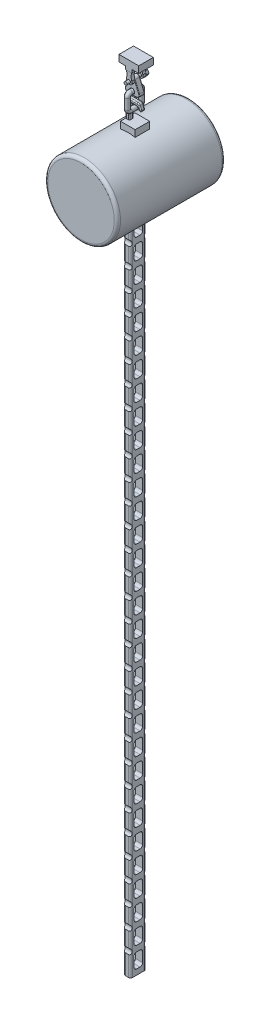
SolidWorks part; units mm, degrees
ref_plane "Alzado" through (0, 0, 0) normal (0, 0, 1) x (1, 0, 0)
ref_plane "Planta" through (0, 0, 0) normal (0, 1, 0) x (1, 0, 0)
ref_plane "Vista lateral" through (0, 0, 0) normal (1, 0, 0) x (0, 0, -1)
sketch "Croquis1" plane through (0, 0, 0) normal (0, 0, 1) x (1, 0, 0)
  line L0 (6.35, 0) -> (-6.35, 0)
  line L1 (-6.35, 0) -> (-6.35, 6.35)
  line L2 (-6.35, 6.35) -> (-19.05, 6.35)
  line L3 (-19.05, 6.35) -> (-19.05, 19.05)
  line L4 (-19.05, 19.05) -> (19.05, 19.05)
  line L5 (0, 0) -> (0, 22.2425) construction
  line L6 (19.05, 6.35) -> (19.05, 19.05)
  line L7 (6.35, 6.35) -> (19.05, 6.35)
  line L8 (6.35, 0) -> (6.35, 6.35)
  point P9 (0, 19.05)
  dimension "D1" = 6.35
  dimension "D2" = 6.35
  dimension "D3" = 12.7
  dimension "D4" = 12.7
extrude "Saliente-Extruir1" add sketch "Croquis1" along normal blind 28
sketch "Croquis2" plane through (0, 0, 0) normal (0, -1, 0) x (1, 0, 0)
  line L0 (0, 28) -> (0, 14) construction
  line L1 (-6.35, 28) -> (6.35, 28) construction
  line L2 (0, 14) -> (6.35, 14) construction
  line L3 (6.35, 28) -> (6.35, 0) construction
  line L4 (-5.35, 6.3567) -> (5.35, 0.3567) construction
  line L5 (-5.35, 27.6433) -> (5.35, 27.6433)
  line L6 (-5.35, 27.6433) -> (-5.35, 21.6433)
  line L7 (-5.35, 21.6433) -> (5.35, 21.6433)
  line L8 (5.35, 27.6433) -> (5.35, 21.6433)
  line L9 (-5.35, 27.6433) -> (5.35, 21.6433) construction
  line L10 (-5.35, 21.6433) -> (5.35, 27.6433) construction
  line L11 (-5.35, 0.3567) -> (5.35, 6.3567) construction
  line L12 (5.35, 0.3567) -> (5.35, 6.3567)
  line L13 (-5.35, 6.3567) -> (5.35, 6.3567)
  line L14 (-5.35, 0.3567) -> (-5.35, 6.3567)
  line L15 (-5.35, 0.3567) -> (5.35, 0.3567)
  point P5 (0, 24.6433)
  point P17 (0, 3.3567)
  dimension "D1" = 10.7
  dimension "D2" = 6
extrude "Saliente-Extruir2" add sketch "Croquis2" along normal blind 21
fillet "Redondeo1" radius 1 2 edges at (-6.35, 0, 14) (6.35, 0, 14)
sketch "Croquis3" plane through (0, 0, 27.6433) normal (0, 0, 1) x (1, 0, 0)
  line L0 (0, -21) -> (0, 0) construction
  line L2 (5.35, -21) -> (5.35, 0) construction
  line L3 (5.35, -21) -> (-5.35, -21) construction
  line L4 (5.35, 0) -> (6.5203, -7.32)
  line L5 (6.5203, -7.32) -> (5.35, -13.669)
  line L6 (-5.35, 0) -> (-6.6992, -7.32)
  line L7 (-6.6992, -7.32) -> (-5.35, -13.669)
  arc A0 (-5.35, 0) -> (-5.35, -13.669) centre (-21.7362, -6.8345) cw
  arc A1 (5.35, 0) -> (5.35, -13.669) centre (21.7362, -6.8345) ccw
extrude "Cortar-Extruir1" cut sketch "Croquis3" against normal up to surface (27.2866 mm away) up to face at (0, -10.5, 0.3567)
fillet "Redondeo2" radius 3 4 edges at (-5.35, -21, 24.6433) (-5.35, -21, 3.3567) (5.35, -21, 3.3567) (5.35, -21, 24.6433)
sketch "Croquis5" plane through (0, 0, 27.6433) normal (0, 0, 1) x (1, 0, 0)
  line L0 (5.35, -16.6157) -> (-5.35, -16.6157) construction
  line L1 (5.35, -18) -> (5.35, -13.669) construction
  line L2 (-5.35, -18) -> (-5.35, -13.669) construction
  circle A0 centre (0, -16.6157) radius 2.8157
extrude "Cortar-Extruir2" cut sketch "Croquis5" against normal up to surface (27.2866 mm away) up to face at (0, -13.3226, 0.3567)
sketch "Croquis6" plane through (0, 0, 0.3567) normal (0, 0, -1) x (-1, 0, 0)
  line L1 (5.7735, -16.6157) -> (2.8868, -11.6157)
  line L2 (2.8868, -11.6157) -> (-2.8868, -11.6157)
  line L3 (-2.8868, -11.6157) -> (-5.7735, -16.6157)
  line L4 (-5.7735, -16.6157) -> (-2.8868, -21.6157)
  line L5 (-2.8868, -21.6157) -> (2.8868, -21.6157)
  line L6 (2.8868, -21.6157) -> (5.7735, -16.6157)
  circle A0 centre (0, -16.6157) radius 5 construction
  dimension "D1" = 10
extrude "Saliente-Extruir3" add sketch "Croquis6" along normal blind 5.5
sketch "Croquis7" plane through (0, 0, 0.3567) normal (0, 0, 1) x (1, 0, 0)
  circle A0 centre (0, -16.6157) radius 2.8157
extrude "Saliente-Extruir4" add sketch "Croquis7" along normal blind 34
sketch "Croquis8" plane through (0, 0, 21.6433) normal (0, 0, -1) x (-1, 0, 0)
  line L0 (4.9336, -14.5464) -> (13.2179, -34.2982)
  line L1 (7.6849, -42.6189) -> (-7.6849, -42.6189)
  line L2 (0, -16.6157) -> (0, -42.6189) construction
  line L3 (-4.9336, -14.5464) -> (-13.2179, -34.2982)
  circle A0 centre (0, -16.6157) radius 2.8157
  arc A1 (4.9336, -14.5464) -> (-4.9336, -14.5464) centre (0, -16.6157) ccw
  arc A2 (-13.2179, -34.2982) -> (-7.6849, -42.6189) centre (-7.6849, -36.6189) ccw
  arc A3 (13.2179, -34.2982) -> (7.6849, -42.6189) centre (7.6849, -36.6189) cw
  point P11 (-16.7078, -42.6189)
  point P14 (16.7078, -42.6189)
  dimension "D1" = 6
extrude "Saliente-Extruir5" add sketch "Croquis8" along normal blind 10
sketch "Croquis9" plane through (0, 0, 11.6433) normal (0, 0, -1) x (-1, 0, 0)
  line L0 (0, -42.6189) -> (0, -35.8189) construction
  line L1 (-7.6849, -42.6189) -> (7.6849, -42.6189) construction
  circle A0 centre (0, -35.8189) radius 4.7625
  dimension "D2" = 9.525
  dimension "D1" = 6.8
extrude "Cortar-Extruir3" cut sketch "Croquis9" against normal blind 10
fillet "Redondeo3" radius 1 11 edges at (-9.284, -24.9187, 21.6433) (-12.6811, -39.9413, 21.6433) (0, -42.6189, 21.6433) (12.6811, -39.9413, 21.6433) (0, -11.2657, 11.6433) (-9.0758, -24.4223, 11.6433) (-12.6811, -39.9413, 11.6433) (0, -42.6189, 11.6433) (12.6811, -39.9413, 11.6433) (9.284, -24.9187, 21.6433) (9.0758, -24.4223, 11.6433)
sketch "Croquis10" plane through (0, 0, 11.6433) normal (0, 0, -1) x (-1, 0, 0)
  circle A0 centre (0, -35.8189) radius 4.35
  dimension "D1" = 8.7
extrude "Saliente-Extruir6" add sketch "Croquis10" against normal blind 11 separate body
sketch3d "Croquis3D1"
  line L0 (0, -35.8189, 22.6433) -> (0, -35.8189, 25.6433)
  line L1 (0, -35.8189, 22.6433) -> (0, -35.8189, 11.6433) construction
  line L2 (0, -40.8189, 30.6433) -> (0, -60.8189, 30.6433)
  line L3 (0, -65.8189, 25.6433) -> (0, -65.8189, 8.6433)
  line L4 (0, -60.8189, 3.6433) -> (0, -40.8189, 3.6433)
  line L5 (0, -35.8189, 8.6433) -> (0, -35.8189, 11.6433)
  arc A0 (0, -65.8189, 8.6433) -> (0, -60.8189, 3.6433) centre (0, -60.8189, 8.6433) ccw
  arc A1 (0, -60.8189, 30.6433) -> (0, -65.8189, 25.6433) centre (0, -60.8189, 25.6433) ccw
  arc A2 (0, -35.8189, 8.6433) -> (0, -40.8189, 3.6433) centre (0, -40.8189, 8.6433) ccw
  arc A3 (0, -35.8189, 25.6433) -> (0, -40.8189, 30.6433) centre (0, -40.8189, 25.6433) ccw
  point P10 (0, -65.8189, 3.6433)
  point P11 (5, -60.8189, 8.6433)
  point P14 (0, -65.8189, 30.6433)
  point P15 (5, -60.8189, 25.6433)
  point P18 (0, -35.8189, 3.6433)
  point P19 (-5, -40.8189, 8.6433)
  point P22 (0, -35.8189, 30.6433)
  point P23 (5, -40.8189, 25.6433)
  dimension "D6" = 5
  dimension "D1" = 8
  dimension "D2" = 30
  dimension "D3" = 30
  dimension "D4" = 27
  dimension "D5" = 8
sketch "Croquis11" plane through (0, 0, 22.6433) normal (0, 0, 1) x (1, 0, 0)
  circle A0 centre (0, -35.8189) radius 4.35
sweep "Barrer1" add profiles "Croquis11" path "Croquis3D1"
sketch "Croquis12" plane through (0, 0, 11.6433) normal (0, 0, -1) x (-1, 0, 0)
  line L0 (-5.8187, -59.4028) -> (5.3811, -59.4028)
  line L1 (7.3811, -61.4028) -> (7.3811, -89.4179)
  line L2 (7.3811, -89.4179) -> (-13.6866, -89.4179)
  line L3 (-13.6866, -89.4179) -> (-13.6866, -100.9297)
  line L4 (-13.6866, -100.9297) -> (14.5883, -100.9297)
  line L5 (14.5883, -100.9297) -> (14.5883, -57.5965)
  line L6 (9.5883, -52.5965) -> (-7.4054, -52.5965)
  line L7 (-12.0568, -55.7621) -> (-14.8153, -62.757)
  line L8 (-13.6885, -65.3513) -> (-13.6003, -65.3861)
  line L9 (-11.3416, -64.8197) -> (-7.3435, -60.1087)
  arc A0 (14.5883, -57.5965) -> (9.5883, -52.5965) centre (9.5883, -57.5965) ccw
  arc A1 (-14.8153, -62.757) -> (-13.6885, -65.3513) centre (-12.9547, -63.4907) ccw
  arc A2 (-13.6003, -65.3861) -> (-11.3416, -64.8197) centre (-12.8665, -63.5255) ccw
  arc A3 (-5.8187, -59.4028) -> (-7.3435, -60.1087) centre (-5.8187, -61.4028) ccw
  arc A4 (5.3811, -59.4028) -> (7.3811, -61.4028) centre (5.3811, -61.4028) cw
  arc A5 (-7.4054, -52.5965) -> (-12.0568, -55.7621) centre (-7.4054, -57.5965) ccw
  dimension "D1" = 5
  dimension "D2" = 2
  dimension "D3" = 5
extrude "Saliente-Extruir7" add sketch "Croquis12" against normal blind 8 separate body
sketch "Croquis13" plane through (0, 0, 11.6433) normal (0, 0, -1) x (-1, 0, 0)
  line L1 (-13.6866, -89.4179) -> (14.5883, -89.4179)
  line L2 (-13.6866, -89.4179) -> (-13.6866, -100.9297)
  line L3 (-13.6866, -100.9297) -> (14.5883, -100.9297)
  line L4 (14.5883, -89.4179) -> (14.5883, -100.9297)
extrude "Saliente-Extruir8" add sketch "Croquis13" along normal blind 10
sketch "Croquis14" plane through (0, 0, 19.6433) normal (0, 0, 1) x (1, 0, 0)
  line L1 (13.6866, -89.4179) -> (-14.5883, -89.4179)
  line L2 (13.6866, -89.4179) -> (13.6866, -100.9297)
  line L3 (13.6866, -100.9297) -> (-14.5883, -100.9297)
  line L4 (-14.5883, -89.4179) -> (-14.5883, -100.9297)
extrude "Saliente-Extruir9" add sketch "Croquis14" along normal blind 10
fillet "Redondeo4" radius 2 26 edges at (-14.5883, -73.5072, 11.6433) (-13.1239, -54.0609, 11.6433) (-1.0915, -52.5965, 11.6433) (-7.3811, -75.4103, 11.6433) (-6.7953, -59.9886, 11.6433) (0.2188, -59.4028, 11.6433) (6.6588, -59.5878, 11.6433) (9.3426, -62.4642, 11.6433) (12.38, -65.4655, 11.6433) (13.6444, -65.3687, 11.6433) (14.7892, -64.2875, 11.6433) (13.436, -59.2596, 11.6433) (-14.5883, -73.5072, 19.6433) (-13.1239, -54.0609, 19.6433) (-1.0915, -52.5965, 19.6433) (10.2186, -53.463, 19.6433) (13.436, -59.2596, 19.6433) (14.7892, -64.2875, 19.6433) (13.6444, -65.3687, 19.6433) (12.38, -65.4655, 19.6433) (9.3426, -62.4642, 19.6433) (6.6588, -59.5878, 19.6433) (-7.3811, -75.4103, 19.6433) (-6.7953, -59.9886, 19.6433) (10.2186, -53.463, 11.6433) (0.2188, -59.4028, 19.6433)
sketch "Croquis15" plane through (0, 0, 1.6433) normal (0, 0, -1) x (-1, 0, 0)
  line L0 (0.4509, -100.9297) -> (0.4509, -170.9297) construction
  line L1 (-13.6866, -100.9297) -> (14.5883, -100.9297) construction
  line L2 (-13.6866, -100.9297) -> (-13.6866, -102.3722)
  line L3 (14.5883, -100.9297) -> (14.5883, -102.3722)
  line L4 (14.5883, -100.9297) -> (-13.6866, -100.9297)
  arc A0 (-13.6866, -102.3722) -> (14.5883, -102.3722) centre (0.4509, -170.9297) ccw
  dimension "D1" = 70
extrude "Saliente-Extruir10" add sketch "Croquis15" against normal up to surface (28 mm away) up to face at (-0.4509, -95.1738, 29.6433)
sketch "Croquis21" plane through (0, 0, 1.6433) normal (0, 0, -1) x (-1, 0, 0)
  circle A0 centre (0.4509, -170.9297) radius 70
extrude "Saliente-Extruir15" add sketch "Croquis21" along normal blind 90
sketch "Croquis22" plane through (0, 0, 29.6433) normal (0, 0, 1) x (1, 0, 0)
  circle A0 centre (-0.4509, -170.9297) radius 70
extrude "Saliente-Extruir16" add sketch "Croquis22" along normal blind 90
fillet "Redondeo6" radius 6 2 edges at (-70.4509, -170.9297, -88.3567) (69.5491, -170.9297, 119.6433)
sketch "Croquis23" plane through (0, 0, 1.6433) normal (0, 0, -1) x (-1, 0, 0)
  line L1 (-9.5491, -243.6811) -> (10.4509, -243.6811)
  line L2 (-9.5491, -243.6811) -> (-9.5491, -238.1783)
  line L3 (-9.5491, -238.1783) -> (10.4509, -238.1783)
  line L4 (10.4509, -243.6811) -> (10.4509, -238.1783)
  line L5 (-9.5491, -243.6811) -> (10.4509, -238.1783) construction
  line L6 (-9.5491, -238.1783) -> (10.4509, -243.6811) construction
  circle A0 centre (0.4509, -170.9297) radius 70 construction
  point P0 (0.4509, -240.9297)
  dimension "D1" = 20
extrude "Saliente-Extruir17" add sketch "Croquis23" against normal blind 30
sketch "Croquis24" plane through (0, -243.6811, 0) normal (0, -1, 0) x (1, 0, 0)
  line L0 (-10.4509, 1.6433) -> (9.5491, 1.6433) construction
  line L1 (-6.9335, 31.6433) -> (6.9335, 31.6433)
  line L2 (-6.9335, 31.6433) -> (-6.9335, 1.6433)
  line L3 (-6.9335, 1.6433) -> (6.9335, 1.6433)
  line L4 (6.9335, 31.6433) -> (6.9335, 1.6433)
  line L5 (-6.9335, 31.6433) -> (6.9335, 1.6433) construction
  line L6 (-6.9335, 1.6433) -> (6.9335, 31.6433) construction
  point P0 (0, 16.6433)
extrude "Saliente-Extruir18" add sketch "Croquis24" along normal blind 1265
sketch "Croquis25" plane through (6.9335, 0, 0) normal (1, 0, 0) x (0, 0, -1)
  line L0 (-16.6433, -243.6811) -> (-16.6433, -262.6811) construction
  line L1 (-31.6433, -243.6811) -> (-1.6433, -243.6811) construction
  line L3 (-19.8806, -276.8669) -> (-13.406, -276.8669)
  line L4 (-24.8806, -271.8669) -> (-24.8806, -253.4953)
  line L5 (-19.8806, -248.4953) -> (-13.406, -248.4953)
  line L6 (-8.406, -271.8669) -> (-8.406, -253.4953)
  line L7 (-24.8806, -276.8669) -> (-8.406, -248.4953) construction
  line L8 (-24.8806, -248.4953) -> (-8.406, -276.8669) construction
  arc A0 (-19.8806, -276.8669) -> (-24.8806, -271.8669) centre (-19.8806, -271.8669) cw
  arc A1 (-13.406, -276.8669) -> (-8.406, -271.8669) centre (-13.406, -271.8669) ccw
  arc A2 (-13.406, -248.4953) -> (-8.406, -253.4953) centre (-13.406, -253.4953) cw
  arc A3 (-24.8806, -253.4953) -> (-19.8806, -248.4953) centre (-19.8806, -253.4953) cw
  arc A4 (-13.406, -276.8669) -> (-8.406, -271.8669) centre (-13.406, -271.8669) ccw
  arc A5 (-13.406, -276.8669) -> (-8.406, -271.8669) centre (-13.406, -271.8669) ccw
  dimension "D2" = 5
  dimension "D3" = 5
  dimension "D4" = 5
  dimension "D1" = 19
extrude "Cortar-Extruir5" cut sketch "Croquis25" against normal up to surface (13.8669 mm away) contours A3 L4 A0 L3 A1 L6 A2 L5 region at (6.9335, -262.6811, 16.6433) up to face at (-6.9335, -876.1811, 16.6433)
pattern_linear "MatrizL1" count 32 spacing 39.4 along (0, -1, 0) of "Cortar-Extruir5"
fillet "Redondeo7" radius 4 4 edges at (-6.9335, -876.1811, 31.6433) (6.9335, -876.1811, 31.6433) (-6.9335, -876.1811, 1.6433) (6.9335, -876.1811, 1.6433)
sketch "Croquis26" plane through (6.9335, 0, 0) normal (1, 0, 0) x (0, 0, -1)
  line L0 (-31.6433, -1508.6811) -> (-31.6433, -243.6811) construction
  line L1 (-16.6433, -276.8669) -> (-16.6433, -287.8953) construction
  line L2 (-19.8806, -276.8669) -> (-13.406, -276.8669) construction
  line L3 (-19.8806, -287.8953) -> (-13.406, -287.8953) construction
  line L4 (-31.6433, -277.4425) -> (-35.143, -281.6436)
  line L5 (-35.143, -281.6436) -> (-31.6433, -288.3186)
  line L6 (-1.6433, -277.4425) -> (1.5597, -282.8805)
  line L7 (1.5597, -282.8805) -> (-1.6433, -288.3186)
  arc A0 (-31.6433, -277.4425) -> (-31.6433, -288.3186) centre (-34.8462, -282.8805) cw
  arc A1 (-1.6433, -277.4425) -> (-1.6433, -288.3186) centre (1.5597, -282.8805) ccw
extrude "Cortar-Extruir6" cut sketch "Croquis26" against normal blind 20
pattern_linear "MatrizL2" count 31 spacing 39.4 along (0, -1, 0) of "Cortar-Extruir6"
